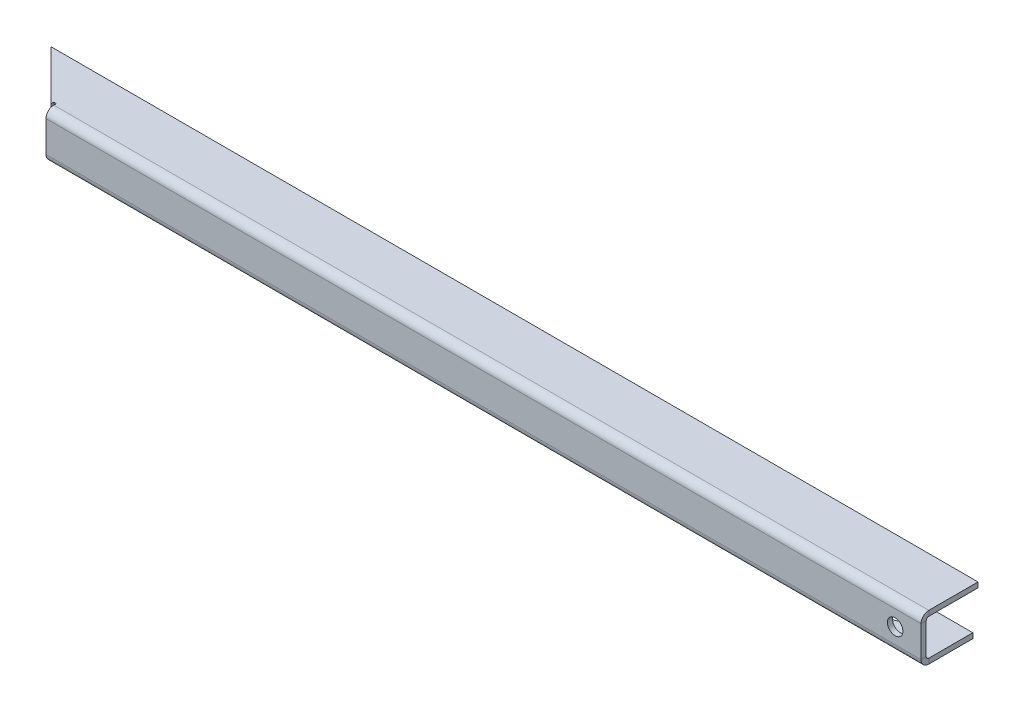
SolidWorks part; units mm, degrees
note: The reader was unsure of these and kept them because the rebuilt part matched: flange length of "Edge-Flange1", "Edge-Flange2".
material "St.37"
ref_plane "Front Plane" through (0, 0, 0) normal (0, 0, 1) x (1, 0, 0)
ref_plane "Top Plane" through (0, 0, 0) normal (0, 1, 0) x (1, 0, 0)
ref_plane "Right Plane" through (0, 0, 0) normal (1, 0, 0) x (0, 0, -1)
sketch "Sketch1" plane through (0, 0, 0) normal (0, 1, 0) x (1, 0, 0)
  line L0 (-84.5, 0) -> (84.5, 0)
  line L1 (-84.5, 0) -> (-94.5, 10)
  line L3 (-94.5, 10) -> (84.5, 10)
  line L4 (84.5, 0) -> (84.5, 10)
  point P3 (0, 0)
  dimension "D1" = 169
  dimension "D2" = 135
  dimension "D3" = 10
base flange "Base-Flange1" sketch "Sketch1" thickness 1 reverse thickness direction no parameters "D1"=1
edge flange "Edge-Flange1" sketch "Sketch8" flange angle 90 flange length 8 flange position material outside bend radius 0.5 thickness 1 relief rectangular parameters "D6"=10
sketch "Sketch8" plane through (0, -1, 0) normal (0, 0, 1) x (-1, 0, 0)
  line L2 (-84.5, 0) -> (-84.5, 7)
  line L3 (-84.5, 7) -> (84.5, 7)
  line L4 (84.5, 7) -> (84.5, 0)
  line L7 (84.5, 0) -> (-84.5, 0) construction
  line L8 (84.5, 0) -> (-84.5, 0)
bend "EdgeBend1" bend radius 0.5 bend angle 90 parameters "D5"=1
edge flange "Edge-Flange2" sketch "Sketch11" flange angle 90 flange length 10 flange position material outside bend radius 0.5 thickness 1 relief rectangular parameters "D6"=10
sketch "Sketch11" plane through (0, -8, 0) normal (0, -1, 0) x (-1, 0, 0)
  line L2 (-84.5, 0) -> (-84.5, 9)
  line L3 (-84.5, 9) -> (84.5, 9)
  line L4 (84.5, 9) -> (84.5, 0)
  line L7 (84.5, 0) -> (-84.5, 0) construction
  line L8 (84.5, 0) -> (-84.5, 0)
bend "EdgeBend2" bend radius 0.5 bend angle 90 parameters "D5"=2
sketch "Sketch12" plane through (0, -9, 0) normal (0, -1, 0) x (1, 0, 0)
  line L0 (-84.5, -0.5) -> (-84.5, -9) construction
  line L1 (-84.5, -9) -> (84.5, -9) construction
  line L2 (84.5, -9) -> (84.5, -0.5) construction
  circle A0 centre (-74.5, -5) radius 1.5
  circle A1 centre (0, -5) radius 1.5
  circle A2 centre (74.5, -5) radius 1.5
  dimension "D2" = 3
  dimension "D1" = 10
  dimension "D3" = 4
  dimension "D5" = 10
  dimension "D4" = 3
extrude "Cut-Extrude1" cut sketch "Sketch12" against normal blind 3 normal cut yes
sketch "Sketch13" plane through (0, 0, 0) normal (0, 0, -1) x (-1, 0, 0)
  line L0 (-84.5, -7.5) -> (-84.5, -1.5) construction
  line L1 (-84.5, -1) -> (94.5, -1) construction
  circle A0 centre (-79.5, -4.5) radius 1.5
  dimension "D2" = 3
  dimension "D1" = 5
  dimension "D3" = 3.5
extrude "Cut-Extrude2" cut sketch "Sketch13" against normal blind 3 normal cut yes
sketch "Bend-Lines1" [suppressed] plane through (0, 0, 0) normal (0, 1, 0) x (1, 0, 0)
sketch "Bounding-Box1" [suppressed] plane through (0, 0, 0) normal (0, 1, 0) x (1, 0, 0)
sheet metal parameters "Sheet-Metal1" thickness 1 parameters "D1"=1
flat pattern "Flat-Pattern1" [suppressed]
sketch "Bend-Lines2" plane through (0, 0, 0) normal (0, 1, 0) x (1, 0, 0)
sketch3d "Bounding-Box2" [suppressed]
  line L0 (-70, 10, 0) -> (70, 10, 0) construction
  line L1 (-70, 0, 0) -> (70, 0, 0) construction
  line L2 (-70, 10, 0) -> (-70, 0, 0) construction
  line L3 (70, 10, 0) -> (70, 0, 0) construction
sheet metal parameters "Sheet-Metal2" thickness 1 parameters "D1"=1
flat pattern "Flat-Pattern1"
sketch "Bend-Lines2" plane through (0, 0, 0) normal (0, 1, 0) x (1, 0, 0)
  line L0 (-60, -0.2854) -> (60, -0.2854) construction
  line L1 (-60, -0.2854) -> (60, -0.2854) construction
sketch3d "Bounding-Box2" [suppressed]
  line L0 (70, 10, 0) -> (-70, 10, 0) construction
  line L1 (70, -7.5708, 0) -> (-70, -7.5708, 0) construction
  line L2 (70, 10, 0) -> (70, -7.5708, 0) construction
  line L3 (-70, 10, 0) -> (-70, -7.5708, 0) construction
bend of the flat pattern "Flatten-<EdgeBend1>1"
sheet metal parameters "Sheet-Metal3" thickness 1 parameters "D1"=1
flat pattern "Flat-Pattern1"
sketch "Bend-Lines2" plane through (0, 0, 0) normal (0, 1, 0) x (1, 0, 0)
  line L0 (-60, -0.2854) -> (60, -0.2854) construction
  line L1 (-60, -0.2854) -> (60, -0.2854) construction
  line L2 (-60, -7.7489) -> (60, -7.7489) construction
  line L3 (-60, -7.7489) -> (60, -7.7489) construction
sketch3d "Bounding-Box2" [suppressed]
  line L0 (70, 10, 0) -> (-70, 10, 0) construction
  line L1 (70, -16.927, 0) -> (-70, -16.927, 0) construction
  line L2 (70, 10, 0) -> (70, -16.927, 0) construction
  line L3 (-70, 10, 0) -> (-70, -16.927, 0) construction
bend of the flat pattern "Flatten-<EdgeBend1>1"
bend of the flat pattern "Flatten-<EdgeBend2>1"
sheet metal parameters "Sheet-Metal4" thickness 1 parameters "D1"=1
flat pattern "Flat-Pattern1"
sketch "Bend-Lines2" plane through (0, 0, 0) normal (0, 1, 0) x (1, 0, 0)
  line L0 (-60, -0.2854) -> (60, -0.2854) construction
  line L1 (-60, -0.2854) -> (60, -0.2854) construction
  line L2 (-60, -7.8562) -> (60, -7.8562) construction
  line L3 (-60, -7.8562) -> (60, -7.8562) construction
sketch3d "Bounding-Box2" [suppressed]
  line L0 (70, 10, 0) -> (-70, 10, 0) construction
  line L1 (70, -17.1416, 0) -> (-70, -17.1416, 0) construction
  line L2 (70, 10, 0) -> (70, -17.1416, 0) construction
  line L3 (-70, 10, 0) -> (-70, -17.1416, 0) construction
bend of the flat pattern "Flatten-<EdgeBend1>1"
bend of the flat pattern "Flatten-<EdgeBend2>1"
sheet metal parameters "Sheet-Metal5" thickness 1 parameters "D1"=1
flat pattern "Flat-Pattern1"
sketch "Bend-Lines2" plane through (0, 0, 0) normal (0, 1, 0) x (1, 0, 0)
  line L0 (-84.5, -0.2854) -> (84.5, -0.2854) construction
  line L1 (-84.5, -0.2854) -> (84.5, -0.2854) construction
  line L2 (-84.5, -7.8562) -> (84.5, -7.8562) construction
  line L3 (-84.5, -7.8562) -> (84.5, -7.8562) construction
sketch3d "Bounding-Box2" [suppressed]
  line L0 (84.5, 10, 0) -> (-94.5, 10, 0) construction
  line L1 (84.5, -17.1416, 0) -> (-94.5, -17.1416, 0) construction
  line L2 (84.5, 10, 0) -> (84.5, -17.1416, 0) construction
  line L3 (-94.5, 10, 0) -> (-94.5, -17.1416, 0) construction
bend of the flat pattern "Flatten-<EdgeBend1>1"
bend of the flat pattern "Flatten-<EdgeBend2>1"
